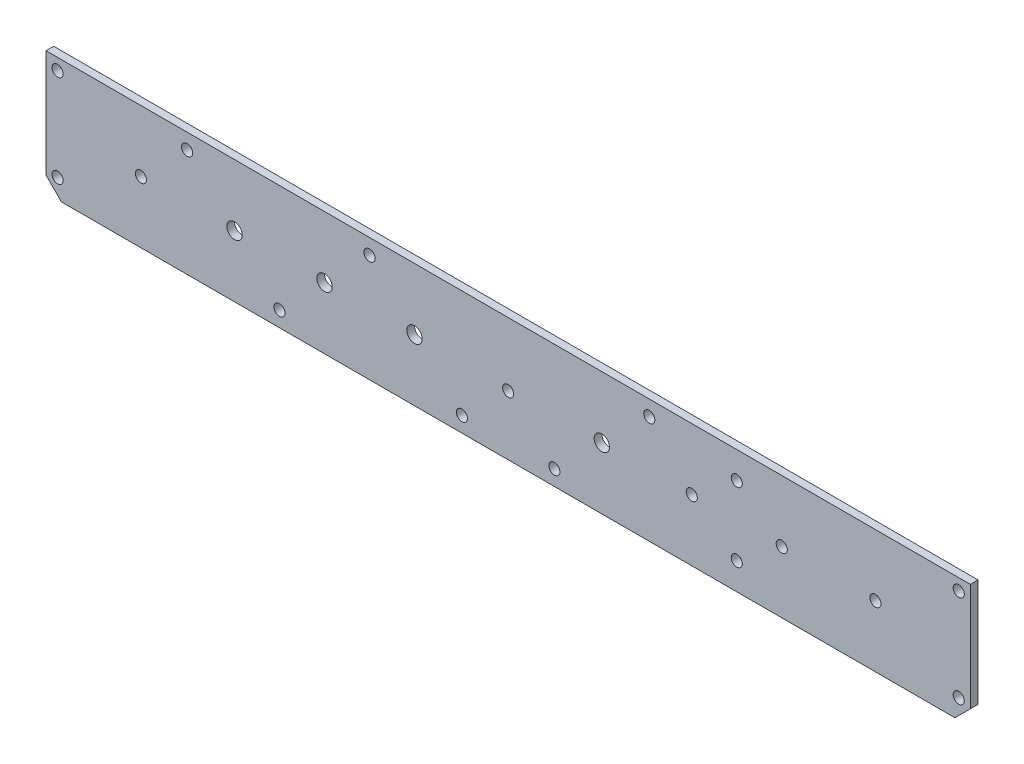
SolidWorks part; units mm, degrees
ref_plane "Front Plane" through (0, 0, 0) normal (0, 0, 1) x (1, 0, 0)
ref_plane "Top Plane" through (0, 0, 0) normal (0, 1, 0) x (1, 0, 0)
ref_plane "Right Plane" through (0, 0, 0) normal (1, 0, 0) x (0, 0, -1)
sketch "Sketch1" plane through (0, 0, 0) normal (0, 0, 1) x (1, 0, 0)
  line L1 (0, 0) -> (381, 0)
  line L2 (0, 0) -> (0, 50.8)
  line L3 (0, 50.8) -> (381, 50.8)
  line L4 (381, 0) -> (381, 50.8)
  dimension "D1" = 50.8
  dimension "D2" = 381
extrude "Boss-Extrude1" add sketch "Sketch1" along normal blind 3.175
sketch "Sketch2" plane through (0, 0, 3.175) normal (0, 0, 1) x (1, 0, 0)
  line L0 (77.724, 25.4) -> (114.808, 25.4) construction
  line L1 (190.5, 50.8) -> (190.5, 0) construction
  line L2 (381, 50.8) -> (0, 50.8) construction
  line L3 (0, 0) -> (381, 0) construction
  line L4 (266.192, 25.4) -> (303.276, 25.4) construction
  line L5 (0, 6.35) -> (0, 0)
  line L6 (0, 50.8) -> (0, 0) construction
  line L7 (0, 0) -> (6.35, 0)
  line L8 (6.35, 0) -> (0, 6.35)
  line L9 (381, 0) -> (374.65, 0)
  line L10 (374.65, 0) -> (381, 6.35)
  line L11 (381, 6.35) -> (381, 0)
  circle A0 centre (39.116, 25.4) radius 2.286
  circle A1 centre (190.5, 24.6062) radius 2.286
  circle A2 centre (114.808, 25.4) radius 3.175
  circle A3 centre (77.724, 25.4) radius 3.175
  circle A4 centre (151.892, 25.4) radius 3.175
  circle A5 centre (229.108, 25.4) radius 3.175
  circle A6 centre (303.276, 25.4) radius 2.286
  circle A7 centre (266.192, 25.4) radius 2.286
  circle A8 centre (341.884, 25.4) radius 2.286
  circle A9 centre (58.166, 44.45) radius 2.286
  circle A10 centre (171.45, 6.35) radius 2.286
  circle A11 centre (209.55, 6.35) radius 2.286
  circle A13 centre (133.35, 44.45) radius 2.286
  circle A14 centre (248.666, 44.45) radius 2.286
  circle A15 centre (96.266, 6.35) radius 2.286
  circle A19 centre (4.7625, 46.0375) radius 2.286
  circle A20 centre (4.7625, 7.9375) radius 2.286
  circle A21 centre (376.2375, 7.9375) radius 2.286
  circle A22 centre (376.2375, 46.0375) radius 2.286
  circle A25 centre (284.734, 11.1125) radius 2.286
  circle A26 centre (284.734, 39.6875) radius 2.286
  point P17 (190.5, 25.4)
  point P38 (96.266, 25.4)
  point P49 (284.734, 25.4)
  dimension "D2" = 4.572
  dimension "D5" = 6.35
  dimension "D7" = 4.572
  dimension "D12" = 4.572
  dimension "D15" = 4.572
  dimension "D16" = 4.572
  dimension "D19" = 4.572
  dimension "D21" = 6.35
  dimension "D27" = 4.572
  dimension "D29" = 11.1125
  dimension "D8" = 4.572
  dimension "D3" = 38.608
  dimension "D4" = 0.7937
  dimension "D6" = 14.2875
  dimension "D22" = 6.35
  dimension "D25" = 4.7625
  dimension "D26" = 4.7625
  dimension "D28" = 7.9375
extrude "Cut-Extrude1" cut sketch "Sketch2" against normal up to next
